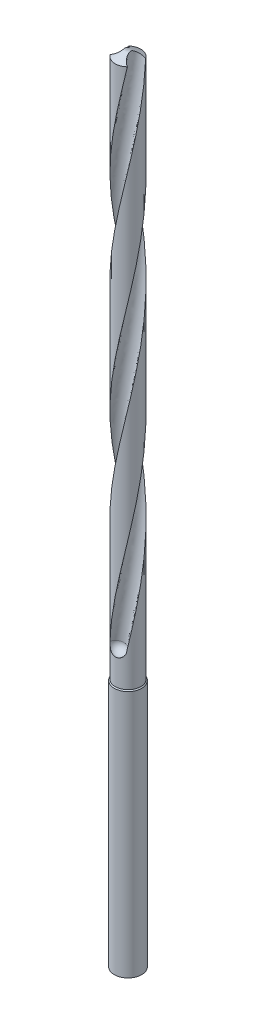
SolidWorks part; units mm, degrees
material "Titanium Ti-13V-11Cr-3Al Solution Treated"
ref_plane "Front Plane" through (0, 0, 0) normal (0, 0, 1) x (1, 0, 0)
ref_plane "Top Plane" through (0, 0, 0) normal (0, 1, 0) x (1, 0, 0)
ref_plane "Right Plane" through (0, 0, 0) normal (1, 0, 0) x (0, 0, -1)
sketch "Sketch1" plane through (0, 0, 0) normal (0, 1, 0) x (1, 0, 0)
  circle A0 centre (0, 0) radius 0.5905
  dimension "D1" = 1.1811
extrude "Boss-Extrude1" add sketch "Sketch1" along normal blind 25.4
chamfer "Chamfer2" distance 0.5906 angle 31 1 edges at (0, 25.4, 0.5905) first distance on face at (0, 25.4, 0.5905)
ref_plane "Plane1" through (0, 25.4, 0) normal (0, 1, 0) x (1, 0, 0)
sketch "Sketch4" plane through (0, 25.4, 0) normal (0, 1, 0) x (1, 0, 0)
  circle A1 centre (0, 0) radius 0.508
  dimension "D1" = 1.016
curve "Helix/Spiral1" pitch 19.05 height 23.8125 radius 0.508 centre (0, 25.4, 0) axis (0, -1, 0) start towards (1, 0, 0)
sketch "Sketch6" plane through (0, 25.4, 0) normal (0, 1, 0) x (1, 0, 0)
  circle A0 centre (0, 0) radius 0.508 construction
  circle A1 centre (0, 0) radius 0.508
curve "Helix/Spiral2" pitch 19.05 height 23.8125 radius 0.508 centre (0, 25.4, 0) axis (0, -1, 0) start towards (0, 0, 1)
sweep "Cut-Sweep1" cut path "Helix/Spiral1" align with end faces yes circular profile diameter 0.762 parameters "D3"=0.762
sweep "Cut-Sweep2" cut path "Helix/Spiral2" circular profile diameter 0.762 parameters "D3"=0.762
sketch "Sketch80" plane through (0, 25.4, 0) normal (0, 1, 0) x (1, 0, 0)
  line L0 (0.137, -0.1074) -> (0.2309, -0.5436)
  line L1 (-0.137, 0.1074) -> (-0.2309, 0.5436)
  arc A0 (-0.492, -0.3266) -> (0.4027, -0.4319) centre (0, 0) ccw construction
  arc A1 (0.492, 0.3266) -> (-0.4027, 0.4319) centre (0, 0) ccw construction
  arc A2 (-0.492, -0.3266) -> (0.4027, -0.4319) centre (0, 0) ccw
  arc A3 (0.492, 0.3266) -> (-0.4027, 0.4319) centre (0, 0) ccw
  spline S0 degree 3 poles (1768.1075, 931.4788) (-56.3854, 57.035) (-3.4665, -2.9977) (-0.2087, -0.2142) (-0.1813, -0.1797) (-0.1412, -0.0987) (-0.1287, -0.0515) (-0.1253, 0.0521) (-0.1334, 0.1003) (-0.1593, 0.188) (-0.1776, 0.2279) (-2.5637, 3.963) (-57.808, -25.8304) (388.0614, -1960.7743) knots -11.712562 -11.712562 -11.712562 -11.712562 0.25 0.25 0.375 0.375 0.5 0.5 0.625 0.625 0.75 0.75 13.216764 13.216764 13.216764 13.216764 only from (-0.492, -0.3266) to (-0.4027, 0.4319) construction
  spline S1 degree 3 poles (-1768.1075, -931.4788) (56.3854, -57.035) (3.4665, 2.9977) (0.2087, 0.2142) (0.1813, 0.1797) (0.1412, 0.0987) (0.1287, 0.0515) (0.1253, -0.0521) (0.1334, -0.1003) (0.1593, -0.188) (0.1776, -0.2279) (2.5637, -3.963) (57.808, 25.8304) (-388.0614, 1960.7743) knots -11.712562 -11.712562 -11.712562 -11.712562 0.25 0.25 0.375 0.375 0.5 0.5 0.625 0.625 0.75 0.75 13.216764 13.216764 13.216764 13.216764 only from (0.492, 0.3266) to (0.4027, -0.4319) construction
  spline S2 degree 3 poles (-0.492, -0.3266) (-0.3988, -0.3307) (-0.3097, -0.3006) (-0.2087, -0.2142) (-0.1813, -0.1797) (-0.1412, -0.0987) (-0.1287, -0.0515) (-0.1253, 0.0521) (-0.1334, 0.1003) (-0.1593, 0.188) (-0.1776, 0.2279) (-0.2487, 0.3391) (-0.3173, 0.3998) (-0.4027, 0.4319) knots 0 0 0 0 0.25 0.25 0.375 0.375 0.5 0.5 0.625 0.625 0.75 0.75 1 1 1 1
  spline S3 degree 3 poles (0.492, 0.3266) (0.3988, 0.3307) (0.3097, 0.3006) (0.2087, 0.2142) (0.1813, 0.1797) (0.1412, 0.0987) (0.1287, 0.0515) (0.1253, -0.0521) (0.1334, -0.1003) (0.1593, -0.188) (0.1776, -0.2279) (0.2487, -0.3391) (0.3173, -0.3998) (0.4027, -0.4319) knots 0 0 0 0 0.25 0.25 0.375 0.375 0.5 0.5 0.625 0.625 0.75 0.75 1 1 1 1
sketch "Sketch99" plane through (-0.2587, 1.5442, 0) normal (-0.1652, 0.9863, 0) x (0.9863, 0.1652, 0)
  line L0 (0.6401, 0.4582) -> (-0.1154, 0.4582) construction
  line L1 (0.6401, 0.4582) -> (-0.1154, 0.4582)
  arc A0 (-0.1154, 0.4582) -> (0.6401, 0.4582) centre (0.2623, 0.508) ccw construction
  arc A1 (-0.1154, 0.4582) -> (0.6401, 0.4582) centre (0.2623, 0.508) ccw
revolve "Cut-Revolve2" cut sketch "Sketch99" angle 360 about L0
sketch "Sketch100" plane through (0.2587, 1.5442, 0) normal (0.1652, 0.9863, 0) x (0.9863, -0.1652, 0)
  line L0 (0.1154, -0.4582) -> (-0.6401, -0.4582) construction
  line L1 (0.1154, -0.4582) -> (-0.6401, -0.4582)
  arc A0 (0.1154, -0.4582) -> (-0.6401, -0.4582) centre (-0.2623, -0.508) ccw construction
  arc A1 (0.1154, -0.4582) -> (-0.6401, -0.4582) centre (-0.2623, -0.508) ccw
revolve "Cut-Revolve3" cut sketch "Sketch100" angle 360 about L0
sketch "Sketch105" plane through (0, 0, 0) normal (0, -1, 0) x (1, 0, 0)
  circle A0 centre (0, 0) radius 0.635
  dimension "D1" = 1.27
extrude "Boss-Extrude2" add sketch "Sketch105" along normal blind 11.43
chamfer "Chamfer3" distance 0.0889 angle 45 1 edges at (0, 0, 0.5905)
sketch3d "3DSketch1"
  circle A0 centre (0, -11.43, 0) radius 0.635 construction
  circle A1 centre (0, -11.43, 0) radius 0.635
  circle A2 centre (0, 0.0889, 0) radius 0.5905 construction
  circle A3 centre (0, 0.0889, 0) radius 0.5905
  point P2 (0, -12.065, 0)
  point P4 (0, -12.065, 0)
  point P8 (0, 0.6795, 0)
  point P11 (0, 0.6795, 0)
  dimension "D1" = 1.1811
  dimension "D2" = 36.83
